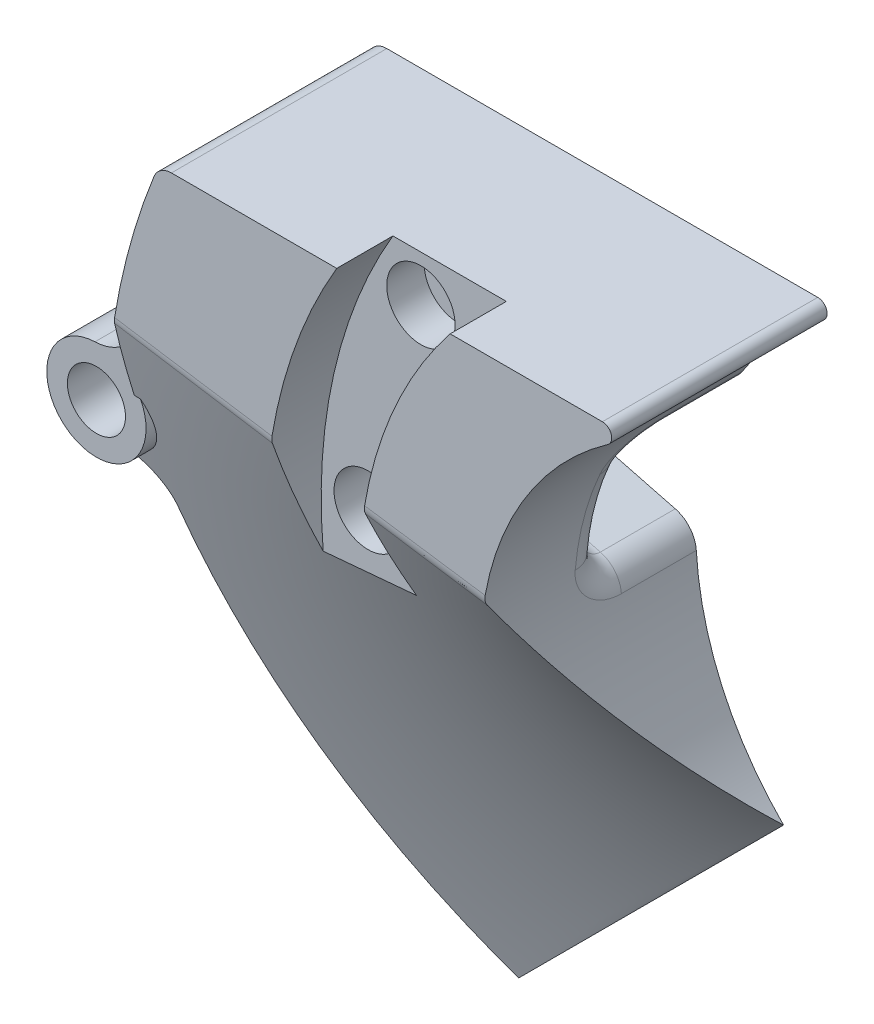
SolidWorks part; units mm, degrees
material "Acrylic (Medium-high impact) 丙烯酸纤维"
ref_plane "前视基准面" through (0, 0, 0) normal (0, 0, 1) x (1, 0, 0)
ref_plane "上视基准面" through (0, 0, 0) normal (0, 1, 0) x (1, 0, 0)
ref_plane "右视基准面" through (0, 0, 0) normal (1, 0, 0) x (0, 0, -1)
sketch "草图1" plane through (0, 0, 0) normal (0, 0, 1) x (1, 0, 0)
  line L0 (0, 72) -> (-135.6698, 72) construction
  line L5 (-15.4919, 28) -> (-135.6698, 28)
  line L6 (-32, 0) -> (-72, 0)
  line L7 (-22.6274, -22.6274) -> (-50.9117, -50.9117)
  line L8 (0, 28) -> (-135.6698, 28) construction
  circle A0 centre (0, 0) radius 72
  circle A2 centre (0, 0) radius 32
  dimension "D1" = 144
  dimension "D2" = 40
  dimension "D4" = 45
  dimension "D3" = 44
extrude "凸台-拉伸1" add sketch "草图1" along normal blind 23 contours A2 L5 A0 L6 | A2 L6 A0 L7 region at (-48.4697, 14.5185, 0) region at (-49.125, -20.3482, 0)
sketch "草图5" plane through (0, 0, 0) normal (0, 0, 1) x (1, 0, 0)
  circle A0 centre (0, 0) radius 51
  arc A1 (-66.3325, 28) -> (-50.9117, -50.9117) centre (0, 0) ccw construction
  dimension "D1" = 21
curve "螺旋线/涡状线1" pitch 153.3333 height 23 radius 51 left hand yes centre (0, 0, 0) axis (0, 0, 1) start towards (1, 0, 0)
sketch "草图6" plane through (0, 0, 0) normal (0.7071, -0.7071, 0) x (0, 0, -1)
  line L0 (0, -32) -> (0, -72) construction
  line L1 (0, -82) -> (-43, -82)
  line L2 (0, -82) -> (0, -30)
  line L3 (0, -30) -> (-43, -30)
  line L4 (-43, -82) -> (-43, -30)
  line L5 (-23, -72) -> (0, -72) construction
  line L6 (-23, -32) -> (-23, -72) construction
  dimension "D1" = 30
  dimension "D2" = 10
  dimension "D3" = 20
sweep "切除-扫描1" cut profiles "草图6" path "螺旋线/涡状线1"
sketch "草图8" plane through (0, 0, 23) normal (0, 0, 1) x (1, 0, 0)
  circle A0 centre (0, 0) radius 50 construction
  circle A1 centre (0, 0) radius 55
  circle A2 centre (0, 0) radius 45
  dimension "D1" = 100
  dimension "D2" = 5
  dimension "D3" = 5
extrude "切除-拉伸1" cut sketch "草图8" against normal blind 6
fillet "圆角1" radius 2 2 edges
sketch "草图9" plane through (0, 0, 17) normal (0, 0, 1) x (1, 0, 0)
  line L0 (-44.3505, 23.0874) -> (0, 0) construction
  line L1 (0, 0) -> (-49.9829, 1.3088) construction
  line L2 (0, 0) -> (-22.2701, 0) construction
  circle A0 centre (0, 0) radius 50 construction
  arc A1 (-54.3824, 8.2191) -> (-54.7835, -4.8747) centre (0, 0) ccw construction
  circle A3 centre (-44.3505, 23.0874) radius 1.6
  circle A4 centre (-49.9829, 1.3088) radius 1.6
  dimension "D1" = 5
  dimension "D2" = 3.2
  dimension "D3" = 3.2
  dimension "D4" = 26
  dimension "D5" = 178.5
extrude "切除-拉伸2" cut sketch "草图9" against normal blind 30
sketch "草图10" plane through (0, 0, 17) normal (0, 0, 1) x (1, 0, 0)
  circle A0 centre (-49.9829, 1.3088) radius 3.65
  circle A1 centre (-44.3505, 23.0874) radius 3.65
  dimension "D2" = 7.3
extrude "切除-拉伸3" cut sketch "草图10" against normal blind 4
shell "抽壳1" [suppressed] thickness 7
sketch "草图11" plane through (0, 0, 23) normal (0, 0, 1) x (1, 0, 0)
  line L0 (0, 0) -> (-76, 0) construction
  circle A1 centre (-76, 0) radius 3.1
  circle A2 centre (-76, 0) radius 5.3
  dimension "D2" = 6.2
  dimension "D3" = 2.2
  dimension "D1" = 76
extrude "凸台-拉伸2" add sketch "草图11" along normal blind 20 from surface starting at face at (-48.3829, 1.3088, 0)
fillet "圆角2" radius 5 2 edges at (-71.9205, -3.3834, 9.0097) (-71.9205, 3.3834, 10)
fillet "圆角3" radius 1 1 edges at (-15.4919, 28, 11.5)
fillet "圆角4" radius 2 1 edges at (-66.3325, 28, 11.5)
sketch "草图12" plane through (0, 0, 17) normal (0, 0, 1) x (1, 0, 0)
  line L0 (-44.3505, 23.0874) -> (-49.9829, 1.3088) construction
sketch "草图13" plane through (0, 0, 0) normal (0, 0, -1) x (-1, 0, 0)
  line L0 (0, 0) -> (47.1667, 12.1981) construction
  line L1 (44.3505, 23.0874) -> (49.9829, 1.3088) construction
  line L2 (47.1667, 12.1981) -> (70.9592, 12.1981) construction
  line L4 (18.9737, 28) -> (64.9923, 28) construction
  line L5 (67.3621, 25.4235) -> (28.1192, 15.2746)
  line L6 (67.3621, 25.4235) -> (78.1099, 12.1981)
  line L7 (31.9988, 0.273) -> (78.1099, 12.1981)
  line L8 (28.1192, 15.2746) -> (31.9988, 0.273)
  arc A0 (71.3535, 9.6268) -> (66.8492, 26.7429) centre (0, 0) ccw construction
  arc A1 (22.6274, -22.6274) -> (18.3987, 26.1818) centre (0, 0) ccw construction
  dimension "D1" = 3.5
extrude "切除-拉伸4" cut sketch "草图13" against normal blind 10
fillet "圆角5" radius 2 2 edges at (-51.6203, 5.3475, 10) (-47.7406, 20.349, 10)
fillet "圆角6" radius 3 5 edges at (-31.9988, 0.273, 4) (-31.9923, 0.7028, 9.2233) (-30.9807, 8.0122, 10) (-28.4705, 14.6093, 9.5467) (-28.1192, 15.2746, 4)
